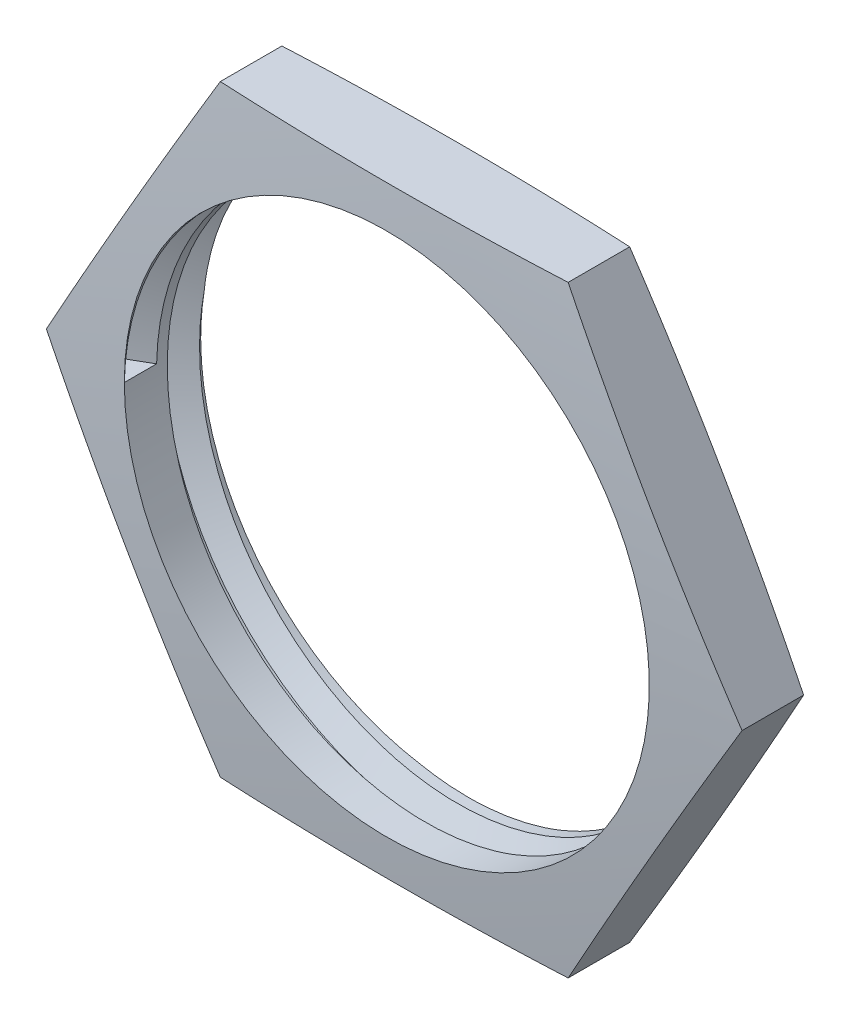
SolidWorks part; units mm, degrees
ref_plane "Front Plane" through (0, 0, 0) normal (0, 0, 1) x (1, 0, 0)
ref_plane "Top Plane" through (0, 0, 0) normal (0, 1, 0) x (1, 0, 0)
ref_plane "Right Plane" through (0, 0, 0) normal (1, 0, 0) x (0, 0, -1)
sketch "Sketch1" plane through (0, 0, 0) normal (0, 0, 1) x (1, 0, 0)
  line L1 (8.0829, 0) -> (4.0415, 7)
  line L2 (4.0415, 7) -> (-4.0415, 7)
  line L3 (-4.0415, 7) -> (-8.0829, 0)
  line L4 (-8.0829, 0) -> (-4.0415, -7)
  line L5 (-4.0415, -7) -> (4.0415, -7)
  line L6 (4.0415, -7) -> (8.0829, 0)
  circle A0 centre (0, 0) radius 7 construction
  circle A1 centre (0, 0) radius 6.1
  dimension "D2" = 12.2
  dimension "D1" = 14
extrude "Boss-Extrude1" add sketch "Sketch1" along normal blind 2.23
sketch "Sketch3" plane through (0, 0, 0) normal (0, 1, 0) x (1, 0, 0)
  line L0 (0, 1.538) -> (0, 0)
  line L1 (-8.0829, -2.23) -> (-8.0829, 0) construction
  line L3 (-8.0829, -0.4) -> (-8.0829, 1.538)
  line L4 (-8.0829, 1.538) -> (0, 1.538)
  line L5 (0, -2.23) -> (0, -3.7459)
  line L6 (4.0415, -2.23) -> (-4.0415, -2.23) construction
  line L7 (-4.0415, -2.23) -> (-8.0829, -2.23) construction
  line L8 (-8.0829, -1.83) -> (-8.0829, -3.7459)
  line L9 (-8.0829, -3.7459) -> (0, -3.7459)
  arc A0 (0, 0) -> (-8.0829, -0.4) centre (0, -81.8667) ccw
  arc A1 (0, -2.23) -> (-8.0829, -1.83) centre (0, 79.6367) cw
  dimension "D1" = 0.4
  dimension "D2" = 0.4
revolve "Cut-Revolve1" cut sketch "Sketch3" angle 360 about L5
thread "Thread1" pitch 1 method cut profile "Thread Profile1" start angle 0, offset 0, length 10, pitch 1, diameter 12.2
ref_plane "Plane1" through (-6.1, 0, 2.0024) normal (0, -1, 0) x (-1, 0, 0)
sketch "Thread Profile1" plane through (-6.1, 0, 2.0024) normal (0, -1, 0) x (-1, 0, 0)
  line L0 (0, 0) -> (0, 1) construction
  line L1 (0, 0) -> (0.5413, 0.3125)
  line L2 (0.5413, 0.3125) -> (0.5413, 0.4375)
  line L3 (0.5413, 0.4375) -> (0, 0.75)
  line L4 (0.5413, 0.375) -> (0, 0.375) construction
  line L11 (0, 0) -> (0, 0.75)
  point P2 (0, 0)
  dimension "Pitch" = 1
  dimension "Profile_Angle" = 60
  dimension "Profile_Land" = 0.125
  dimension "Profile_Height" = 0.5413
